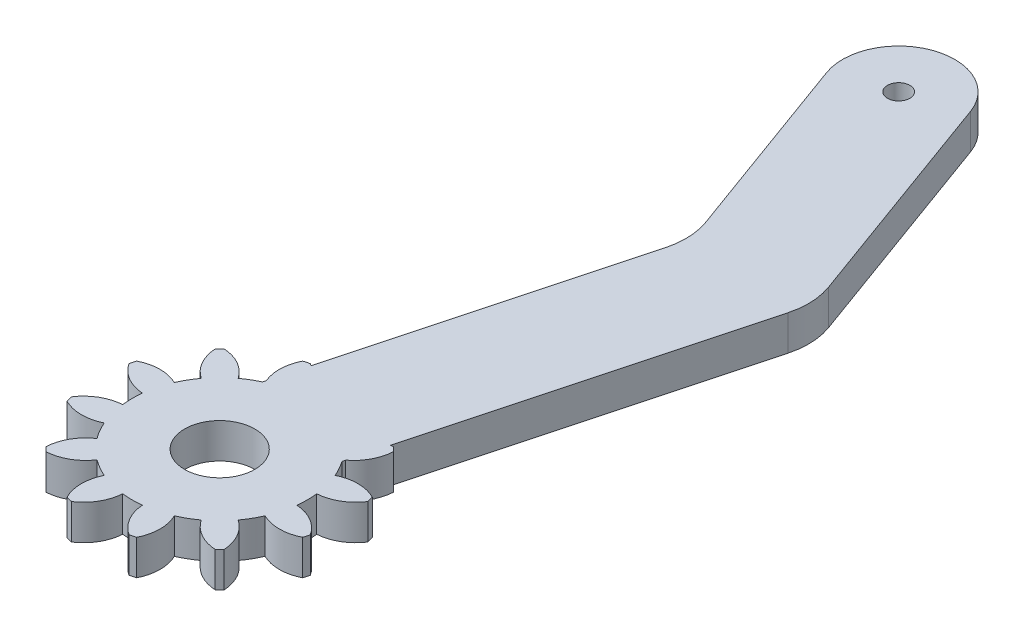
SolidWorks part; units mm, degrees
ref_plane "Front Plane" through (0, 0, 0) normal (0, 0, 1) x (1, 0, 0)
ref_plane "Top Plane" through (0, 0, 0) normal (0, 1, 0) x (1, 0, 0)
ref_plane "Right Plane" through (0, 0, 0) normal (1, 0, 0) x (0, 0, -1)
sketch "Sketch1" plane through (0, 0, 0) normal (0, 1, 0) x (1, 0, 0)
  line L1 (10.2133, 7.2069) -> (24.4653, 60.396)
  line L4 (0, 0) -> (21.2032, 79.1314) construction
  line L5 (7.7048, 59.6643) -> (-5.976, 97.252)
  line L6 (-5.976, 97.252) -> (9.0591, 102.7243)
  line L7 (9.0591, 102.7243) -> (24.4653, 60.396)
  line L8 (7.7048, 59.6643) -> (-5.2415, 11.348)
  line L10 (0, 0) -> (48.1971, 0) construction
  arc A0 (-5.2415, 11.348) -> (10.2133, 7.2069) centre (0, 0) ccw
  point P1 (1.5415, 99.9881)
  dimension "D1" = 25
  dimension "D2" = 16
  dimension "D3" = 100
  dimension "D4" = 16
  dimension "D5" = 145
  dimension "D6" = 40
  dimension "D7" = 75
extrude "Boss-Extrude1" add sketch "Sketch1" along normal blind 5
fillet "Fillet1" 2 edges at (-5.976, 2.5, -97.252) (9.0591, 2.5, -102.7243) type full round first side face at (0.8644, 2.5, -78.4581) second side face at (16.7622, 2.5, -81.5602) middle face at (1.5415, 2.5, -99.9881)
fillet "Fillet2" radius 10 2 edges at (24.4653, 2.5, -60.396) (7.7048, 2.5, -59.6643)
sketch "Sketch2" plane through (0, 5, 0) normal (0, 1, 0) x (1, 0, 0)
  circle A0 centre (4.2777, 92.4706) radius 1.6
  dimension "D1" = 3.2
extrude "Cut-Extrude2" cut sketch "Sketch2" against normal through all contours A0
sketch "Sketch5" plane through (0, 5, 0) normal (0, 1, 0) x (1, 0, 0)
  arc A0 (-12.0517, -12.6888) -> (-7.1035, -9.5148) centre (-12.4017, -6.699) ccw
  arc A1 (-7.1035, -9.5148) -> (-4.6884, -10.9092) centre (0, 0) ccw
  arc A2 (-4.6884, -10.9092) -> (-4.963, -16.7815) centre (0.3993, -14.0897) ccw
  arc A3 (-4.963, -16.7815) -> (-4.0927, -17.0147) centre (0, 0) ccw
  arc A4 (-4.0927, -17.0147) -> (-1.3944, -11.7918) centre (-7.3907, -12.0024) ccw
  arc A5 (-1.3944, -11.7918) -> (1.3944, -11.7918) centre (0, 0) ccw
  arc A6 (1.3944, -11.7918) -> (4.0927, -17.0147) centre (7.3907, -12.0024) ccw
  arc A7 (4.0927, -17.0147) -> (4.963, -16.7815) centre (0, 0) ccw
  arc A8 (4.963, -16.7815) -> (4.6884, -10.9092) centre (-0.3993, -14.0897) ccw
  arc A9 (4.6884, -10.9092) -> (7.1035, -9.5148) centre (0, 0) ccw
  arc A10 (7.1035, -9.5148) -> (12.0517, -12.6888) centre (12.4017, -6.699) ccw
  arc A11 (12.0517, -12.6888) -> (12.6888, -12.0517) centre (0, 0) ccw
  arc A12 (12.6888, -12.0517) -> (9.5148, -7.1035) centre (6.699, -12.4017) ccw
  arc A13 (9.5148, -7.1035) -> (10.9092, -4.6884) centre (0, 0) ccw
  arc A14 (10.9092, -4.6884) -> (16.7815, -4.963) centre (14.0897, 0.3993) ccw
  arc A15 (16.7815, -4.963) -> (17.0147, -4.0927) centre (0, 0) ccw
  arc A16 (17.0147, -4.0927) -> (11.7918, -1.3944) centre (12.0024, -7.3907) ccw
  arc A17 (11.7918, -1.3944) -> (11.7918, 1.3944) centre (0, 0) ccw
  arc A18 (11.7918, 1.3944) -> (17.0147, 4.0927) centre (12.0024, 7.3907) ccw
  arc A19 (17.0147, 4.0927) -> (16.7815, 4.963) centre (0, 0) ccw
  arc A20 (16.7815, 4.963) -> (10.9092, 4.6884) centre (14.0897, -0.3993) ccw
  arc A21 (10.9092, 4.6884) -> (9.5148, 7.1035) centre (0, 0) ccw
  arc A22 (9.5148, 7.1035) -> (12.6888, 12.0517) centre (6.699, 12.4017) ccw
  arc A23 (12.6888, 12.0517) -> (12.0517, 12.6888) centre (0, 0) ccw
  arc A24 (12.0517, 12.6888) -> (7.1035, 9.5148) centre (12.4017, 6.699) ccw
  arc A25 (7.1035, 9.5148) -> (4.6884, 10.9092) centre (0, 0) ccw
  arc A26 (4.6884, 10.9092) -> (4.963, 16.7815) centre (-0.3993, 14.0897) ccw
  arc A27 (4.963, 16.7815) -> (4.0927, 17.0147) centre (0, 0) ccw
  arc A28 (4.0927, 17.0147) -> (1.3944, 11.7918) centre (7.3907, 12.0024) ccw
  arc A29 (1.3944, 11.7918) -> (-1.3944, 11.7918) centre (0, 0) ccw
  arc A30 (-1.3944, 11.7918) -> (-4.0927, 17.0147) centre (-7.3907, 12.0024) ccw
  arc A31 (-4.0927, 17.0147) -> (-4.963, 16.7815) centre (0, 0) ccw
  arc A32 (-4.963, 16.7815) -> (-4.6884, 10.9092) centre (0.3993, 14.0897) ccw
  arc A33 (-4.6884, 10.9092) -> (-7.1035, 9.5148) centre (0, 0) ccw
  arc A34 (-7.1035, 9.5148) -> (-12.0517, 12.6888) centre (-12.4017, 6.699) ccw
  arc A35 (-12.0517, 12.6888) -> (-12.6888, 12.0517) centre (0, 0) ccw
  arc A36 (-12.6888, 12.0517) -> (-9.5148, 7.1035) centre (-6.699, 12.4017) ccw
  arc A37 (-9.5148, 7.1035) -> (-10.9092, 4.6884) centre (0, 0) ccw
  arc A38 (-10.9092, 4.6884) -> (-16.7815, 4.963) centre (-14.0897, -0.3993) ccw
  arc A39 (-16.7815, 4.963) -> (-17.0147, 4.0927) centre (0, 0) ccw
  arc A40 (-17.0147, 4.0927) -> (-11.7918, 1.3944) centre (-12.0024, 7.3907) ccw
  arc A41 (-11.7918, 1.3944) -> (-11.7918, -1.3944) centre (0, 0) ccw
  arc A42 (-11.7918, -1.3944) -> (-17.0147, -4.0927) centre (-12.0024, -7.3907) ccw
  arc A43 (-17.0147, -4.0927) -> (-16.7815, -4.963) centre (0, 0) ccw
  arc A44 (-16.7815, -4.963) -> (-10.9092, -4.6884) centre (-14.0897, 0.3993) ccw
  arc A45 (-10.9092, -4.6884) -> (-9.5148, -7.1035) centre (0, 0) ccw
  arc A46 (-9.5148, -7.1035) -> (-12.6888, -12.0517) centre (-6.699, -12.4017) ccw
  arc A47 (-12.6888, -12.0517) -> (-12.0517, -12.6888) centre (0, 0) ccw
extrude "Boss-Extrude3" add sketch "Sketch5" against normal blind 5
sketch "Sketch6" plane through (0, 5, 0) normal (0, 1, 0) x (1, 0, 0)
  circle A0 centre (0, 0) radius 5
  dimension "D1" = 10
extrude "Cut-Extrude3" cut sketch "Sketch6" against normal through all
